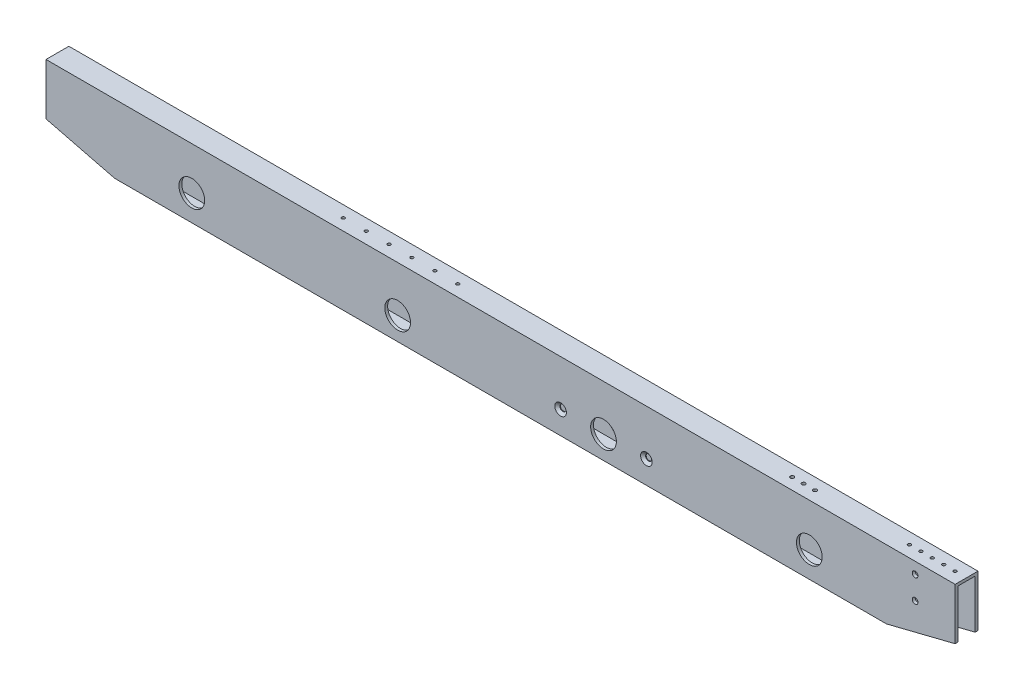
SolidWorks part; units mm, degrees
material "6061-T6 (SS)"
ref_plane "Front Plane" through (0, 0, 0) normal (0, 0, 1) x (1, 0, 0)
ref_plane "Top Plane" through (0, 0, 0) normal (0, 1, 0) x (1, 0, 0)
ref_plane "Right Plane" through (0, 0, 0) normal (1, 0, 0) x (0, 0, -1)
sketch "Sketch1" plane through (0, 0, 0) normal (0, 0, 1) x (1, 0, 0)
  line L0 (0, -12.7) -> (-342.9, -9.525) construction
  line L1 (-504.825, 38.1) -> (504.825, 38.1)
  line L2 (-504.825, 38.1) -> (-504.825, -38.1)
  line L3 (-504.825, -38.1) -> (504.825, -38.1)
  line L4 (504.825, 38.1) -> (504.825, -38.1)
  line L5 (-504.825, 38.1) -> (504.825, -38.1) construction
  line L6 (-504.825, -38.1) -> (504.825, 38.1) construction
  line L7 (-504.825, -38.1) -> (504.825, -38.1) construction
  line L8 (-504.825, -38.1) -> (-504.825, 12.7) construction
  line L9 (-339.7523, -73.025) -> (358.7477, -73.025) construction
  line L10 (-504.825, 12.7) -> (504.825, 12.7) construction
  line L11 (504.825, -38.1) -> (504.825, 12.7) construction
  line L12 (0, -12.7) -> (342.9, -9.525) construction
  line L13 (-114.3, -12.7) -> (114.3, -12.7) construction
  circle A0 centre (-114.3, -12.7) radius 14.2875
  circle A1 centre (114.3, -12.7) radius 14.2875
  circle A2 centre (-342.9, -9.525) radius 14.2875
  circle A3 centre (342.9, -9.525) radius 14.2875
  circle A4 centre (-342.9, -9.525) radius 63.5 construction
  circle A5 centre (-114.3, -12.7) radius 63.5 construction
  circle A6 centre (114.3, -12.7) radius 63.5 construction
  circle A7 centre (342.9, -9.525) radius 63.5 construction
  point P0 (0, 0)
  point P12 (0, -38.1)
  dimension "D5" = 228.6
  dimension "D4" = 50.8
  dimension "D8" = 228.6
  dimension "D9" = 28.575
  dimension "D6" = 28.575
  dimension "D10" = 127
  dimension "D1" = 76.2
  dimension "D2" = 1009.65
  dimension "D3" = 25.4
  dimension "D7" = 228.6
extrude "Boss-Extrude2" add sketch "Sketch1" along normal mid plane 25.4
sketch "Sketch3" plane through (504.825, 0, 0) normal (1, 0, 0) x (0, 0, -1)
  line L8 (9.525, -34.925) -> (9.525, 34.925)
  line L9 (9.525, 34.925) -> (-9.525, 34.925)
  line L10 (-9.525, 34.925) -> (-9.525, -34.925)
  line L11 (-9.525, -34.925) -> (9.525, -34.925)
  line L12 (9.525, -34.925) -> (9.525, 34.925)
  line L13 (9.525, 34.925) -> (-9.525, 34.925)
  line L14 (-9.525, 34.925) -> (-9.525, -34.925)
  line L15 (-9.525, -34.925) -> (9.525, -34.925)
  dimension "D1" = 3.175
extrude "Cut-Extrude2" cut sketch "Sketch3" against normal through all
sketch "Sketch4" plane through (0, 0, 12.7) normal (0, 0, 1) x (1, 0, 0)
  line L0 (-504.825, -38.1) -> (-504.825, -19.05)
  line L1 (-504.825, 38.1) -> (-504.825, -38.1) construction
  line L2 (-504.825, -19.05) -> (-428.625, -38.1)
  line L3 (-504.825, -38.1) -> (504.825, -38.1) construction
  line L4 (-428.625, -38.1) -> (-504.825, -38.1)
  line L5 (0, -38.1) -> (0, 38.1) construction
  line L6 (504.825, 38.1) -> (-504.825, 38.1) construction
  line L7 (428.625, -38.1) -> (504.825, -38.1)
  line L8 (504.825, -38.1) -> (504.825, -19.05)
  line L9 (504.825, -19.05) -> (428.625, -38.1)
  line L11 (504.825, -19.05) -> (504.825, 38.1) construction
  point P15 (0, 0)
  dimension "D1" = 19.05
  dimension "D2" = 57.15
  dimension "D3" = 76.2
  dimension "D4" = 504.825
  dimension "D5" = 14.036
extrude "Cut-Extrude3" cut sketch "Sketch4" against normal through all
sketch "Sketch9" plane through (0, 38.1, 0) normal (0, 1, 0) x (1, 0, 0)
  line L0 (504.825, -12.7) -> (504.825, 12.7) construction
  circle A0 centre (492.125, 0) radius 1.7272
  circle A1 centre (479.425, 0) radius 1.7272
  circle A2 centre (466.725, 0) radius 1.7272
  circle A3 centre (454.025, 0) radius 1.7272
  circle A4 centre (441.325, 0) radius 1.7272
  point P2 (504.825, 0)
  dimension "D1" = 3.4544
  dimension "D2" = 12.7
  dimension "D3" = 4
  dimension "D4" = 2
extrude "Cut-Extrude4" cut sketch "Sketch9" against normal blind 2.54
sketch "Sketch12" plane through (0, 38.1, 0) normal (0, 1, 0) x (1, 0, 0)
  line L0 (-504.825, -12.7) -> (-504.825, 12.7) construction
  circle A0 centre (-187.325, 0) radius 1.7272
  circle A1 centre (-161.925, 0) radius 1.7272
  circle A2 centre (-136.525, 0) radius 1.7272
  circle A3 centre (-111.125, 0) radius 1.7272
  circle A4 centre (-85.725, 0) radius 1.7272
  circle A5 centre (-60.325, 0) radius 1.7272
  point P5 (-28.575, 0)
  point P15 (-504.825, 0)
  dimension "D1" = 3.4544
  dimension "D2" = 317.5
  dimension "D4" = 476.25
  dimension "D3" = 6
extrude "Cut-Extrude7" cut sketch "Sketch12" against normal blind 5.08
hole_wizard "CSK for 1/4 Flat Head Machine Screw (100)2" positions "Sketch16" profile "Sketch15" countersink size "1/4" standard "ANSI Inch" end condition through all
sketch "Sketch16" plane through (0, 0, 12.7) normal (0, 0, 1) x (1, 0, 0)
  circle A0 centre (114.3, -12.7) radius 14.2875 construction
  point P4 (66.675, -12.7)
  point P6 (161.925, -12.7)
  dimension "D1" = 47.625
  dimension "D2" = 47.625
sketch "Sketch15" plane through (66.675, -12.7, 12.7) normal (1, 0, 0) x (0, -1, 0)
  line L0 (0, 0) -> (0, 25.4)
  line L1 (0, 25.4) -> (3.3782, 25.4)
  line L2 (3.3782, 25.4) -> (3.3782, 2.5682)
  line L3 (3.3782, 2.5682) -> (6.4389, 0)
  line L5 (6.4389, 0) -> (0, 0)
  line L6 (-3.3782, 2.5682) -> (-6.4389, 0) construction
  line L11 (0, -6.35) -> (0, 107.95) construction
  dimension "Thru Hole Dia." = 6.7564
  dimension "Thru Hole Depth" = 25.4
  dimension "Near C'Sink Dia." = 12.8778
  dimension "Near C'Sink Angle" = 100
sketch "Sketch17" plane through (0, -38.1, 0) normal (0, -1, 0) x (-1, 0, 0)
  line L2 (504.825, 9.525) -> (504.825, -9.525) construction
  circle A0 centre (-396.875, 0) radius 1.7272
  circle A1 centre (-320.675, 0) radius 1.7272
  circle A2 centre (-244.475, 0) radius 1.7272
  circle A3 centre (-168.275, 0) radius 1.7272
  circle A4 centre (-92.075, 0) radius 1.7272
  circle A5 centre (-15.875, 0) radius 1.7272
  circle A6 centre (60.325, 0) radius 1.7272
  point P2 (504.825, 0)
  dimension "D1" = 3.4544
  dimension "D2" = 444.5
  dimension "D3" = 7
extrude "Cut-Extrude8" cut sketch "Sketch17" against normal blind 6.35
sketch "Sketch18" plane through (0, 0, -12.7) normal (0, 0, -1) x (-1, 0, 0)
  circle A0 centre (-114.3, -12.7) radius 17.4625
  dimension "D1" = 34.925
extrude "Cut-Extrude9" cut sketch "Sketch18" against normal blind 3.81
hole_wizard "1/4 (0.25) Diameter Hole1" positions "Sketch20" profile "Sketch19" hole size "1/4" standard "ANSI Inch" end condition through all
sketch "Sketch20" plane through (0, 0, 12.7) normal (0, 0, 1) x (1, 0, 0)
  line L0 (504.825, -19.05) -> (504.825, 38.1) construction
  line L1 (504.825, 38.1) -> (-504.825, 38.1) construction
  point P0 (460.375, 25.4)
  point P2 (460.375, 0)
  dimension "D1" = 25.4
  dimension "D2" = 44.45
  dimension "D3" = 12.7
sketch "Sketch19" plane through (460.375, 25.4, 12.7) normal (1, 0, 0) x (0, -1, 0)
  line L0 (0, 0) -> (0, 25.4)
  line L1 (0, 25.4) -> (3.175, 25.4)
  line L2 (3.175, 25.4) -> (3.175, 0)
  line L5 (3.175, 0) -> (0, 0)
  line L11 (0, -6.35) -> (0, 107.95) construction
  dimension "Thru Hole Dia." = 6.35
  dimension "Thru Hole Depth" = 25.4
hole_wizard "#10-32 Tapped Hole2" positions "Sketch24" profile "Sketch23" tap size "#10-32" standard "ANSI Inch" end condition through all
sketch "Sketch24" plane through (0, 38.1, 0) normal (0, 1, 0) x (1, 0, 0)
  line L0 (504.825, -12.7) -> (504.825, 12.7) construction
  point P0 (336.55, 0)
  point P2 (323.85, 0)
  point P4 (311.15, 0)
  dimension "D1" = 168.275
  dimension "D2" = 12.7
  dimension "D3" = 12.7
sketch "Sketch23" plane through (336.55, 38.1, 0) normal (1, 0, 0) x (0, 0, 1)
  line L0 (0, 0) -> (0, 76.2)
  line L1 (0, 76.2) -> (2.0193, 76.2)
  line L2 (2.0193, 76.2) -> (2.0193, 0)
  line L5 (2.0193, 0) -> (0, 0)
  line L11 (0, -6.35) -> (0, 107.95) construction
  dimension "Thread Major Dia." = 4.0386
  dimension "Thru Tap Drill Depth" = 76.2
